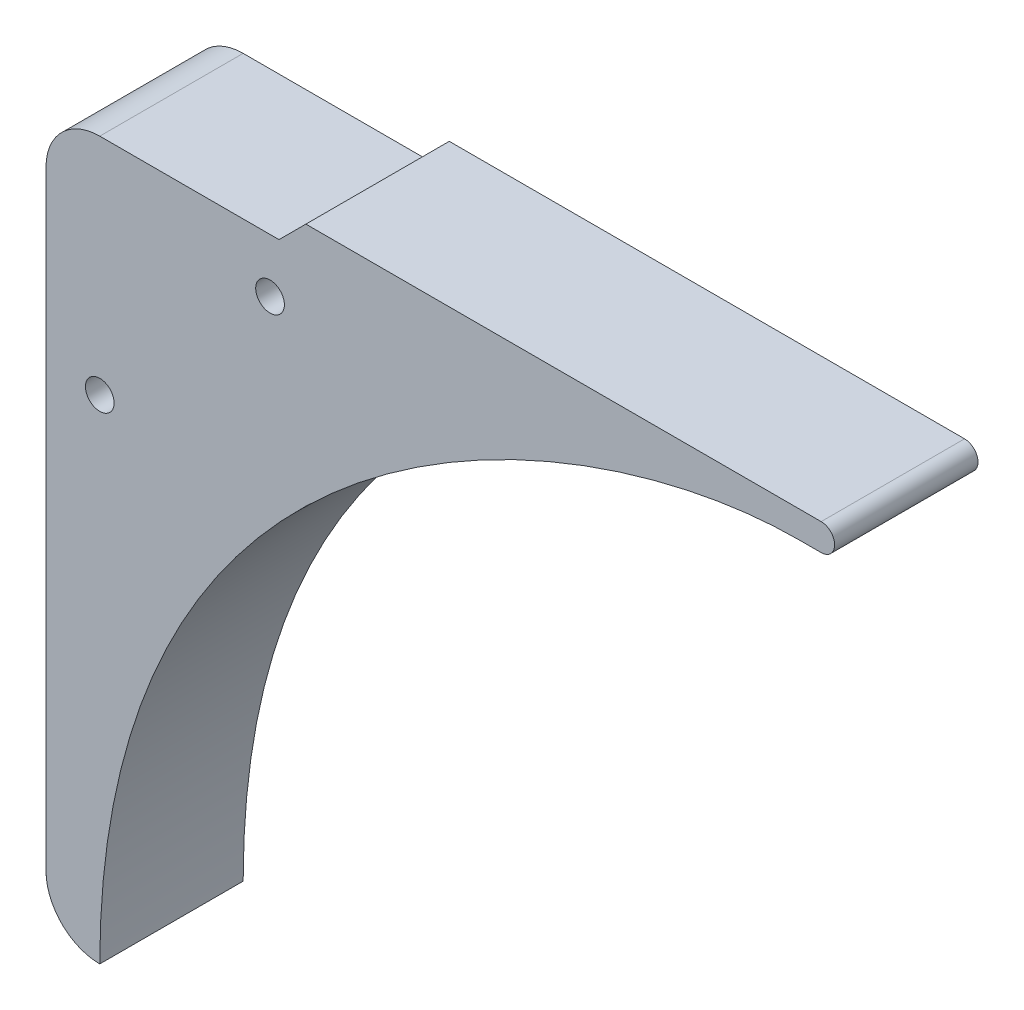
SolidWorks part; units mm, degrees
material "POM Ацеталь кополимер"
ref_plane "Спереди" through (0, 0, 0) normal (0, 0, 1) x (1, 0, 0)
ref_plane "Сверху" through (0, 0, 0) normal (0, 1, 0) x (1, 0, 0)
ref_plane "Справа" through (0, 0, 0) normal (1, 0, 0) x (0, 0, -1)
sketch "Model" plane through (0, 0, 0) normal (0, 0, 1) x (1, 0, 0)
  line L0 (0, 0) -> (13, 0)
  line L1 (0, -40) -> (0, 0)
  line L2 (14.5, 1.5) -> (44, 1.5)
  line L5 (44, 1.5) -> (44, 0)
  line L6 (44, 0) -> (42, 0)
  line L8 (0, -40) -> (3, -40)
  line L9 (13, 0) -> (14.5, 1.5)
  spline S0 degree 3 poles (3, -40) (3, -11.6867) (28.9885, 0) (42, 0) knots 0 0 0 0 0.938492 0.938492 0.938492 0.938492
  dimension "D1" = 2
  dimension "D3" = 40
  dimension "D2" = 1.5
  dimension "D4" = 1.5
  dimension "D5" = 44
  dimension "D6" = 3
  dimension "D7" = 135
  dimension "D8" = 29.5
extrude "База" add sketch "Model" against normal blind 8
fillet "Скругление2" radius 3 1 edges at (0, 0, -4)
fillet "Скругление3" 2 edges at (44, 1.5, -4) (44, 0, -4) type full round first side face at (29.25, 1.5, -4) second side face at (43, 0, -4) middle face at (44, 0.75, -4)
hole_wizard "Крепление M2" positions "Эскиз4" profile "Эскиз5" tap size "M2" standard "DIN" end condition through all
sketch "Эскиз4" plane through (0, 0, 0) normal (0, 0, 1) x (1, 0, 0)
  line L0 (3, -12.5) -> (0, -12.5) construction
  line L1 (0, -3) -> (0, -40) construction
  line L4 (12.5, -3) -> (12.5, 0) construction
  line L7 (12.5, -3) -> (3, -3) construction
  line L8 (3, -3) -> (3, -12.5) construction
  point P0 (3, -12.5)
  point P3 (12.5, -3)
  dimension "D1" = 3
  dimension "D2" = 12.5
sketch "Эскиз5" plane through (3, -12.5, 0) normal (1, 0, 0) x (0, -1, 0)
  line L0 (0, 0) -> (0, 8)
  line L1 (0, 8) -> (0.8, 8)
  line L2 (0.8, 8) -> (0.8, 0)
  line L5 (0.8, 0) -> (0, 0)
  line L11 (0, -6.35) -> (0, 107.95) construction
  dimension "Диаметр проходного сверла" = 1.6
  dimension "Глубина проходного сверла" = 8
cosmetic thread "Отверстие резьбы1" parameters "D2"=2
cosmetic thread "Отверстие резьбы2" parameters "D2"=2
fillet "Скругление4" radius 3 1 edges at (0, -40, -4)
